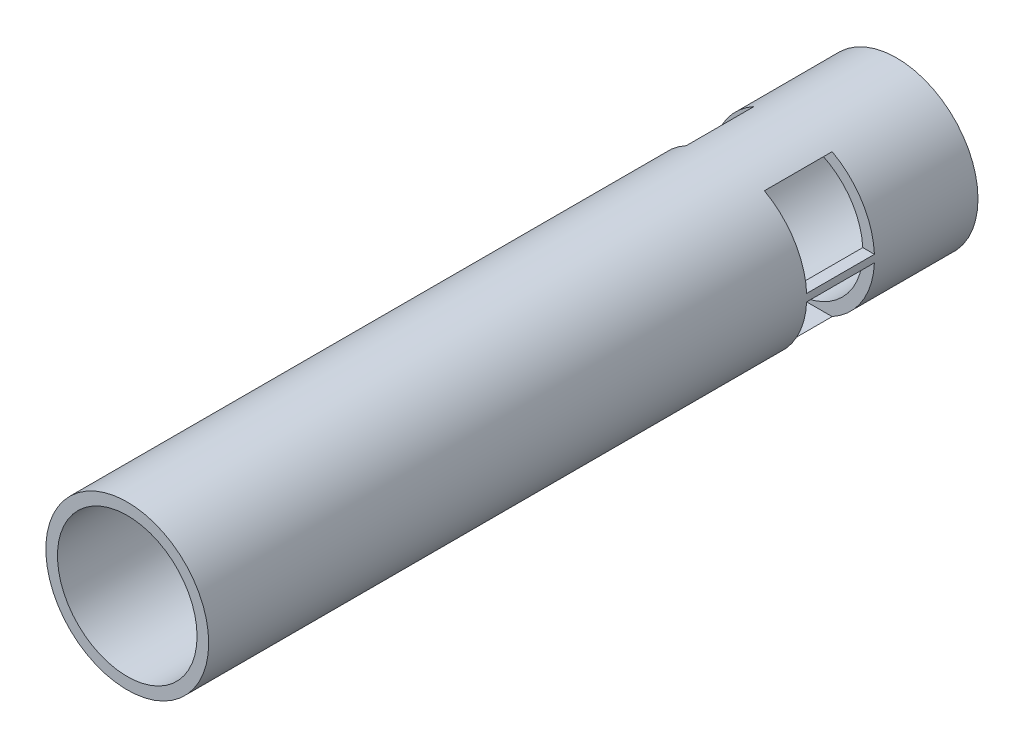
SolidWorks part; units mm, degrees
ref_plane "Front Plane" through (0, 0, 0) normal (0, 0, 1) x (1, 0, 0)
ref_plane "Top Plane" through (0, 0, 0) normal (0, 1, 0) x (1, 0, 0)
ref_plane "Right Plane" through (0, 0, 0) normal (1, 0, 0) x (0, 0, -1)
sketch "Sketch1" plane through (0, 0, 0) normal (0, 0, 1) x (1, 0, 0)
  circle A0 centre (0, 0) radius 38.1
  circle A1 centre (0, 0) radius 44.45
  dimension "D1" = 88.9
  dimension "D2" = 6.35
extrude "Boss-Extrude1" add sketch "Sketch1" along normal blind 420
sketch "Sketch2" plane through (0, 0, 0) normal (1, 0, 0) x (0, 0, -1)
  line L0 (0, 0) -> (-75, 0) construction
  line L1 (-75, 44.45) -> (-75, -44.45) construction
  line L2 (0, 44.45) -> (-420, 44.45) construction
  line L3 (-420, -44.45) -> (0, -44.45) construction
  point P9 (-75, 2)
  point P10 (-75, -2)
  point P11 (-75, -20.5)
  point P12 (-75, 20.5)
  dimension "D1" = 2
  dimension "D2" = 2
  dimension "D3" = 18.5
  dimension "D4" = 18.5
sketch "Sketch3" plane through (0, 0, 0) normal (1, 0, 0) x (0, 0, -1)
  line L1 (-56.5, -39) -> (-93.5, -39)
  line L2 (-56.5, -39) -> (-56.5, -2)
  line L3 (-56.5, -2) -> (-93.5, -2)
  line L4 (-93.5, -39) -> (-93.5, -2)
  line L5 (-56.5, -39) -> (-93.5, -2) construction
  line L6 (-56.5, -2) -> (-93.5, -39) construction
  line L7 (-93.5, 39) -> (-56.5, 39)
  line L8 (-93.5, 39) -> (-93.5, 2)
  line L9 (-93.5, 2) -> (-56.5, 2)
  line L10 (-56.5, 39) -> (-56.5, 2)
  line L11 (-93.5, 39) -> (-56.5, 2) construction
  line L12 (-93.5, 2) -> (-56.5, 39) construction
  point P0 (-75, -20.5)
  point P6 (-75, 20.5)
  dimension "D1" = 37
  dimension "D2" = 37
  dimension "D3" = 37
  dimension "D4" = 37
extrude "Cut-Extrude1" cut sketch "Sketch3" along normal through all and the other way blind 63
